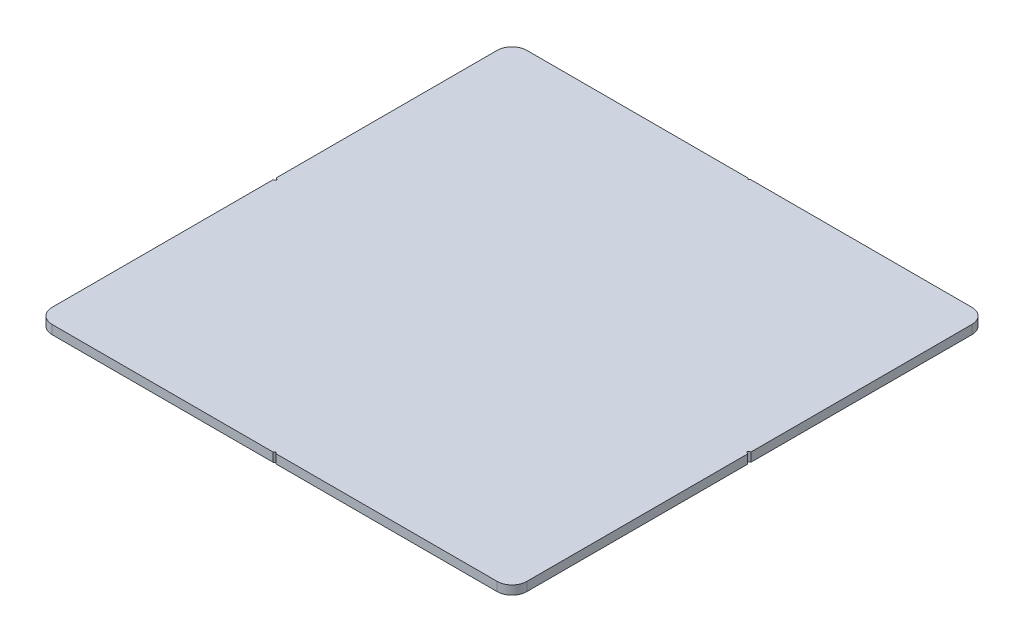
SolidWorks part; units mm, degrees
material "Клен"
ref_plane "Спереди" through (0, 0, 0) normal (0, 0, 1) x (1, 0, 0)
ref_plane "Сверху" through (0, 0, 0) normal (0, 1, 0) x (1, 0, 0)
ref_plane "Справа" through (0, 0, 0) normal (1, 0, 0) x (0, 0, -1)
sketch "Эскиз1" plane through (0, 0, 0) normal (0, 1, 0) x (1, 0, 0)
  line L0 (-199.4521, 0) -> (246.9406, 0) construction
  line L1 (-150, -160) -> (150, -160)
  line L2 (-160, -150) -> (-160, 150)
  line L3 (-150, 160) -> (150, 160)
  line L4 (160, -150) -> (160, 150)
  line L5 (-160, -160) -> (160, 160) construction
  line L6 (-160, 160) -> (160, -160) construction
  line L7 (0, -194.3379) -> (0, 187.7626) construction
  arc A0 (-150, -160) -> (-160, -150) centre (-150, -150) cw
  arc A1 (150, -160) -> (160, -150) centre (150, -150) ccw
  arc A2 (150, 160) -> (160, 150) centre (150, 150) cw
  arc A3 (-160, 150) -> (-150, 160) centre (-150, 150) cw
  point P0 (0, 0)
  dimension "D2" = 10
  dimension "D1" = 320
extrude "Бобышка-Вытянуть1" add sketch "Эскиз1" along normal blind 6
sketch "Эскиз2" plane through (0, 6, 0) normal (0, 1, 0) x (1, 0, 0)
  line L1 (0, -176.9605) -> (0, 172.8451) construction
  line L8 (0, 0) -> (-184.1552, 0) construction
  line L9 (-158.3663, 0) -> (-160, 1.2692)
  line L10 (-160, 150) -> (-160, -150) construction
  line L11 (-160, 1.2692) -> (-160, -1.2752)
  line L12 (-160, -1.2752) -> (-158.3663, 0)
  line L13 (160, -1.2752) -> (158.3663, 0)
  line L14 (160, 1.2692) -> (160, -1.2752)
  line L15 (158.3663, 0) -> (160, 1.2692)
  line L16 (0, 159.0596) -> (0.9404, 160)
  line L17 (150, 160) -> (-150, 160) construction
  line L18 (0.9404, 160) -> (-0.9404, 160)
  line L19 (-0.9404, 160) -> (0, 159.0596)
  line L20 (-0.9404, -160) -> (0, -159.0596)
  line L21 (0.9404, -160) -> (-0.9404, -160)
  line L22 (0, -159.0596) -> (0.9404, -160)
extrude "Вырез-Вытянуть1" cut sketch "Эскиз2" against normal through all
ref_plane "Плоскость1" through (0, 0, 0) normal (1, 0, 0) x (0, 0, -1)
